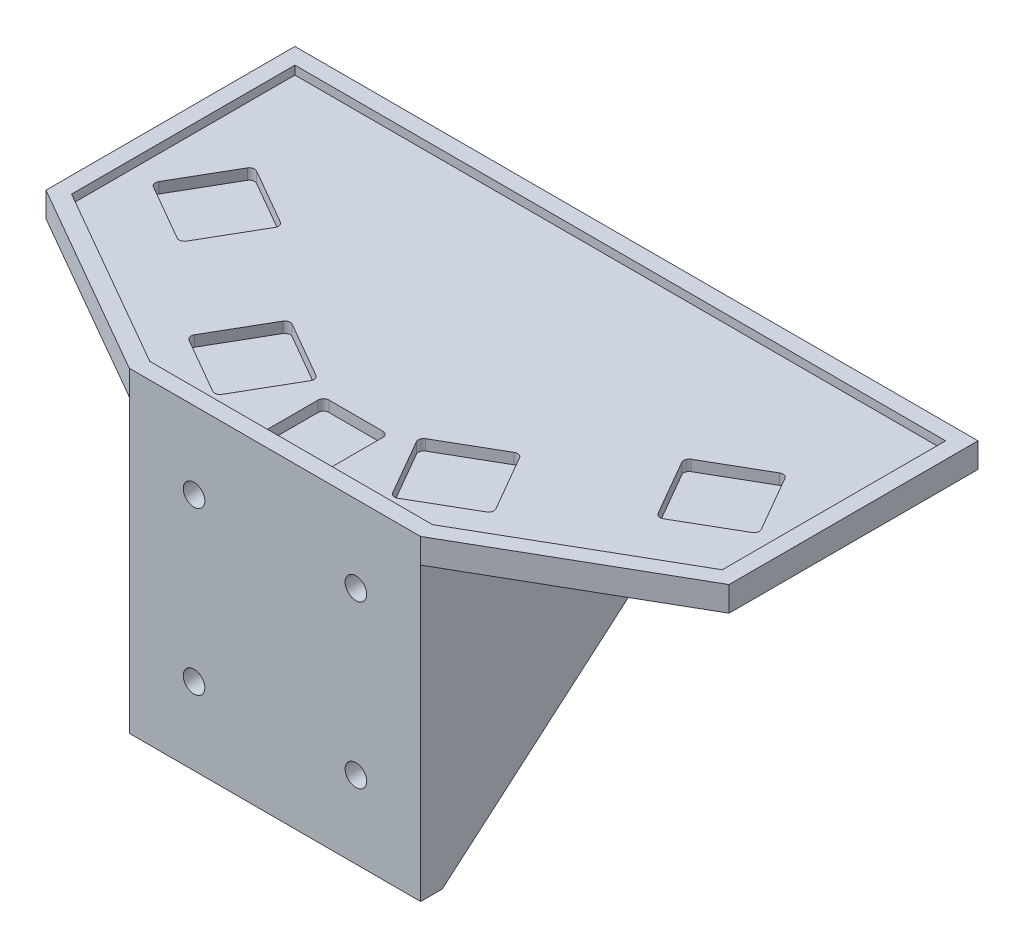
SolidWorks part; units mm, degrees
ref_plane "Спереди" through (0, 0, 0) normal (0, 0, 1) x (1, 0, 0)
ref_plane "Сверху" through (0, 0, 0) normal (0, 1, 0) x (1, 0, 0)
ref_plane "Справа" through (0, 0, 0) normal (1, 0, 0) x (0, 0, -1)
sketch "Эскиз1" plane through (0, 0, 0) normal (0, 1, 0) x (1, 0, 0)
  line L0 (60.3, 0) -> (-60.3, 0)
  line L1 (-60.3, 0) -> (-60.3, -41.4)
  line L2 (-60.3, -41.4) -> (-26.2, -61)
  line L3 (-26.2, -61) -> (26.2, -61)
  line L4 (26.2, -61) -> (60.3, -41.4)
  line L5 (60.3, -41.4) -> (60.3, 0)
  line L6 (0, 0) -> (0, -61) construction
  line L7 (63.3, 3) -> (-63.3, 3)
  line L8 (-63.3, 3) -> (-63.3, -43.1359)
  line L9 (-63.3, -43.1359) -> (-27.0007, -64)
  line L10 (-27.0007, -64) -> (27.0007, -64)
  line L11 (27.0007, -64) -> (63.3, -43.1359)
  line L12 (63.3, -43.1359) -> (63.3, 3)
  line L13 (-3, 0) -> (-3, -61)
  point P4 (0, 0)
  dimension "D1" = 120.6
  dimension "D2" = 41.4
  dimension "D3" = 61
  dimension "D4" = 52.4
  dimension "D5" = 3
extrude "Бобышка-Вытянуть1" add sketch "Эскиз1" along normal blind 1.6 contours L11 L12 L7 L8 L9 L10 L5 L4 L3 L2 L1 L0 region at (61.8676, 0, 20.068)
sketch "Эскиз2" plane through (0, 0, 0) normal (0, -1, 0) x (1, 0, 0)
  line L6 (63.3, 43.1359) -> (27.0007, 64)
  line L7 (27.0007, 64) -> (-27.0007, 64)
  line L8 (-27.0007, 64) -> (-63.3, 43.1359)
  line L9 (-63.3, 43.1359) -> (-63.3, -3)
  line L10 (-63.3, -3) -> (63.3, -3)
  line L11 (63.3, -3) -> (63.3, 43.1359)
  line L12 (63.3, 43.1359) -> (27.0007, 64)
  line L13 (27.0007, 64) -> (-27.0007, 64)
  line L14 (-27.0007, 64) -> (-63.3, 43.1359)
  line L15 (-63.3, 43.1359) -> (-63.3, -3)
  line L16 (-63.3, -3) -> (63.3, -3)
  line L17 (63.3, -3) -> (63.3, 43.1359)
  dimension "D1" = 0
extrude "Бобышка-Вытянуть2" add sketch "Эскиз2" along normal blind 3
sketch "Эскиз3" plane through (0, 0, 0) normal (0, 1, 0) x (1, 0, 0)
  line L0 (-6, -61) -> (6, -61)
  line L1 (-6, -61) -> (-6, -49)
  line L2 (6, -61) -> (6, -49)
  line L3 (-6, -49) -> (6, -49)
  line L4 (-26.2, -61) -> (26.2, -61) construction
  line L5 (0, 0) -> (0, -61) construction
  line L6 (60.3, 0) -> (-60.3, 0) construction
  line L7 (0, -55) -> (60.3, -20.1858) construction
  line L8 (60.3, -41.4) -> (60.3, 0) construction
  line L9 (0, -55) -> (-60.3, -20.1858) construction
  line L10 (-60.3, 0) -> (-60.3, -41.4) construction
  line L11 (-6, -49) -> (6, -61) construction
  line L13 (-21.4365, -39.7369) -> (-9.3122, -46.7369)
  line L14 (-21.4365, -39.7369) -> (-28.4365, -51.8612)
  line L15 (-9.3122, -46.7369) -> (-16.3122, -58.8612)
  line L16 (-28.4365, -51.8612) -> (-16.3122, -58.8612)
  line L17 (9.3122, -46.7369) -> (21.4365, -39.7369)
  line L18 (9.3122, -46.7369) -> (16.3122, -58.8612)
  line L19 (21.4365, -39.7369) -> (28.4365, -51.8612)
  line L20 (16.3122, -58.8612) -> (28.4365, -51.8612)
  line L21 (-15.3744, -43.2369) -> (-16.6244, -45.4019) construction
  line L22 (15.3744, -43.2369) -> (16.6244, -45.4019) construction
  line L23 (56.3275, -30.5622) -> (44.2032, -37.5622)
  line L24 (56.3275, -30.5622) -> (49.3275, -18.4378)
  line L25 (44.2032, -37.5622) -> (37.2032, -25.4378)
  line L26 (49.3275, -18.4378) -> (37.2032, -25.4378)
  line L27 (56.3275, -30.5622) -> (37.2032, -25.4378) construction
  line L28 (44.2032, -37.5622) -> (49.3275, -18.4378) construction
  line L29 (-44.2032, -37.5622) -> (-37.2032, -25.4378)
  line L30 (-44.2032, -37.5622) -> (-56.3275, -30.5622)
  line L31 (-37.2032, -25.4378) -> (-49.3275, -18.4378)
  line L32 (-56.3275, -30.5622) -> (-49.3275, -18.4378)
  line L33 (-44.2032, -37.5622) -> (-49.3275, -18.4378) construction
  line L34 (-37.2032, -25.4378) -> (-56.3275, -30.5622) construction
  point P30 (46.7654, -28)
  point P31 (-46.7654, -28)
  dimension "D1" = 120
  dimension "D2" = 12
  dimension "D3" = 14
  dimension "D4" = 4
  dimension "D5" = 2.5
  dimension "D6" = 4
  dimension "D7" = 54
  dimension "D8" = 54
extrude "Вырез-Вытянуть1" cut sketch "Эскиз3" against normal blind 2
fillet "Скругление1" radius 1 20 edges at (44.2032, -1, 37.5622) (37.2032, -1, 25.4378) (49.3275, -1, 18.4378) (56.3275, -1, 30.5622) (28.4365, -1, 51.8612) (16.3122, -1, 58.8612) (9.3122, -1, 46.7369) (21.4365, -1, 39.7369) (-6, -1, 49) (6, -1, 49) (6, -1, 61) (-6, -1, 61) (-28.4365, -1, 51.8612) (-16.3122, -1, 58.8612) (-9.3122, -1, 46.7369) (-21.4365, -1, 39.7369) (-56.3275, -1, 30.5622) (-44.2032, -1, 37.5622) (-37.2032, -1, 25.4378) (-49.3275, -1, 18.4378)
sketch "Эскиз4" plane through (0, 0, 64) normal (0, 0, 1) x (1, 0, 0)
  line L0 (-27.0007, -3) -> (27.0007, -3)
  line L1 (-27.0007, -3) -> (-27.0007, -57.0015)
  line L2 (27.0007, -3) -> (27.0007, -57.0015)
  line L3 (-27.0007, -57.0015) -> (27.0007, -57.0015)
extrude "Бобышка-Вытянуть3" add sketch "Эскиз4" against normal blind 4
sketch "Эскиз5" plane through (-27.0007, 0, 0) normal (-1, 0, 0) x (0, 0, 1)
  line L0 (60, -3) -> (-3, -3)
  line L1 (-3, -3) -> (60, -57.0015)
  line L2 (60, -57.0015) -> (60, -3)
extrude "Бобышка-Вытянуть4" add sketch "Эскиз5" against normal blind 4
sketch "Эскиз6" plane through (27.0007, 0, 0) normal (1, 0, 0) x (0, 0, -1)
  line L3 (3, -3) -> (-60, -3)
  line L4 (-60, -57.0015) -> (3, -3)
  line L5 (-60, -3) -> (-60, -57.0015)
  line L6 (3, -3) -> (-60, -3)
  line L7 (-60, -57.0015) -> (3, -3)
  line L8 (-60, -3) -> (-60, -57.0015)
  dimension "D1" = 0
extrude "Бобышка-Вытянуть5" add sketch "Эскиз6" against normal blind 4
sketch "Эскиз7" plane through (0, 0, 64) normal (0, 0, 1) x (1, 0, 0)
  line L0 (-27.0007, 1.6) -> (27.0007, -57.0015) construction
  line L2 (15, -12.7007) -> (-15, -12.7007) construction
  line L3 (15, -12.7007) -> (15, -42.7007) construction
  line L4 (15, -42.7007) -> (-15, -42.7007) construction
  line L5 (-15, -12.7007) -> (-15, -42.7007) construction
  line L6 (15, -12.7007) -> (-15, -42.7007) construction
  line L7 (15, -42.7007) -> (-15, -12.7007) construction
  circle A0 centre (-15, -12.7007) radius 2
  circle A1 centre (15, -12.7007) radius 2
  circle A2 centre (15, -42.7007) radius 2
  circle A3 centre (-15, -42.7007) radius 2
  point P4 (0, -27.7007)
  dimension "D2" = 4
  dimension "D1" = 30
extrude "Вырез-Вытянуть2" cut sketch "Эскиз7" against normal through all both and the other way through all
